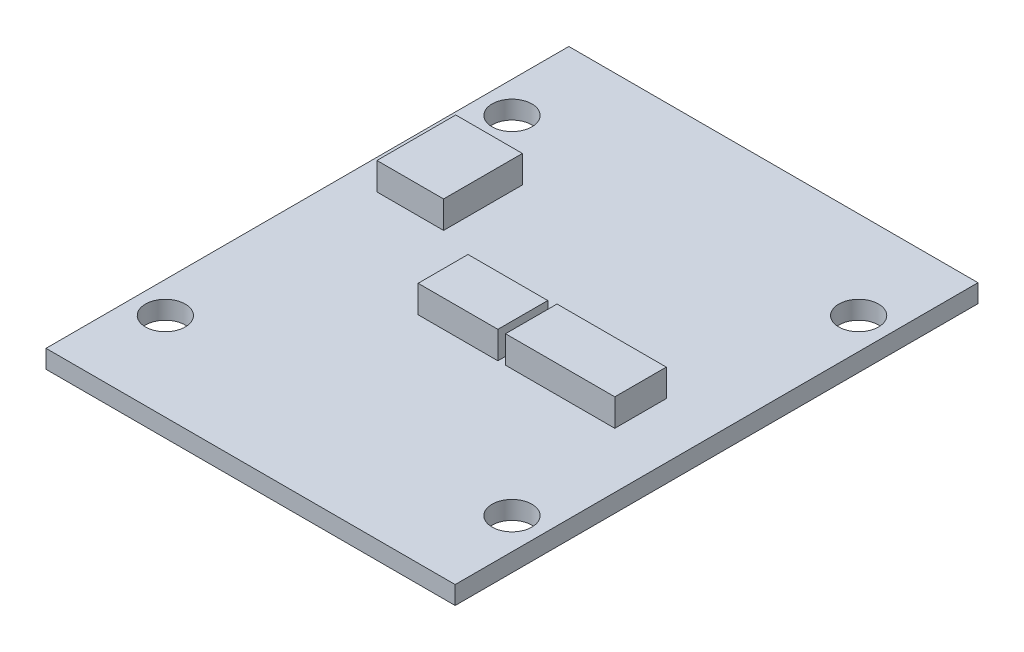
SolidWorks part; units mm, degrees
ref_plane "Front Plane" through (0, 0, 0) normal (0, 0, 1) x (1, 0, 0)
ref_plane "Top Plane" through (0, 0, 0) normal (0, 1, 0) x (1, 0, 0)
ref_plane "Right Plane" through (0, 0, 0) normal (1, 0, 0) x (0, 0, -1)
sketch "Sketch1" plane through (0, 0, 0) normal (0, 1, 0) x (1, 0, 0)
  line L0 (0, 18) -> (0, -18) construction
  line L1 (-18, 23) -> (18, 23)
  line L2 (-18, 23) -> (-18, -23)
  line L3 (-18, -23) -> (18, -23)
  line L4 (18, 23) -> (18, -23)
  line L5 (-18, 23) -> (18, -23) construction
  line L6 (-18, -23) -> (18, 23) construction
  line L7 (18, -18) -> (-18, -18)
  line L8 (18, -18) -> (18, 18)
  line L9 (18, 18) -> (-18, 18)
  line L10 (-18, -18) -> (-18, 18)
  line L11 (18, -18) -> (-18, 18) construction
  line L12 (18, 18) -> (-18, -18) construction
  line L13 (-18, 0) -> (18, 0) construction
  circle A0 centre (-15.25, 15.25) radius 1.75
  circle A1 centre (15.25, 15.25) radius 1.75
  circle A2 centre (-15.25, -15.25) radius 1.75
  circle A3 centre (15.25, -15.25) radius 1.75
  point P0 (0, 0)
  point P6 (0, 0)
  dimension "D3" = 3.5
  dimension "D1" = 46
  dimension "D2" = 36
  dimension "D4" = 30.5
extrude "PCB" add sketch "Sketch1" along normal blind 1.6 contours L9 L4 L1 L2 | L4 L9 L2 L7 A3 A1 A0 A2 | L4 L7 L2 L3 region at (0, 0, -20.5) region at (0, 0, 0) region at (0, 0, 20.5)
sketch "Sketch2" plane through (0, 1.6, 0) normal (0, 1, 0) x (1, 0, 0)
  line L1 (13.118, 0.4566) -> (3.5041, 0.4566)
  line L2 (13.118, 0.4566) -> (13.118, -4.0741)
  line L3 (13.118, -4.0741) -> (3.5041, -4.0741)
  line L4 (3.5041, 0.4566) -> (3.5041, -4.0741)
  line L5 (2.8313, 0.3154) -> (-4.1847, 0.3154)
  line L6 (2.8313, 0.3154) -> (2.8313, -4.0741)
  line L7 (2.8313, -4.0741) -> (-4.1847, -4.0741)
  line L8 (-4.1847, 0.3154) -> (-4.1847, -4.0741)
  line L9 (-15.3548, 10.4054) -> (-9.4909, 10.4054)
  line L10 (-15.3548, 10.4054) -> (-15.3548, 3.472)
  line L11 (-15.3548, 3.472) -> (-9.4909, 3.472)
  line L12 (-9.4909, 10.4054) -> (-9.4909, 3.472)
extrude "Components" add sketch "Sketch2" along normal offset from surface (2.4 mm away) 4 contours L12 L9 L10 L11 | L5 L8 L7 L6 | L1 L4 L3 L2 region at (8.311, 1.6, 1.8087) region at (-0.6767, 1.6, 1.8793) region at (-12.4229, 1.6, -6.9387) up to face at (0, 0, 0)
